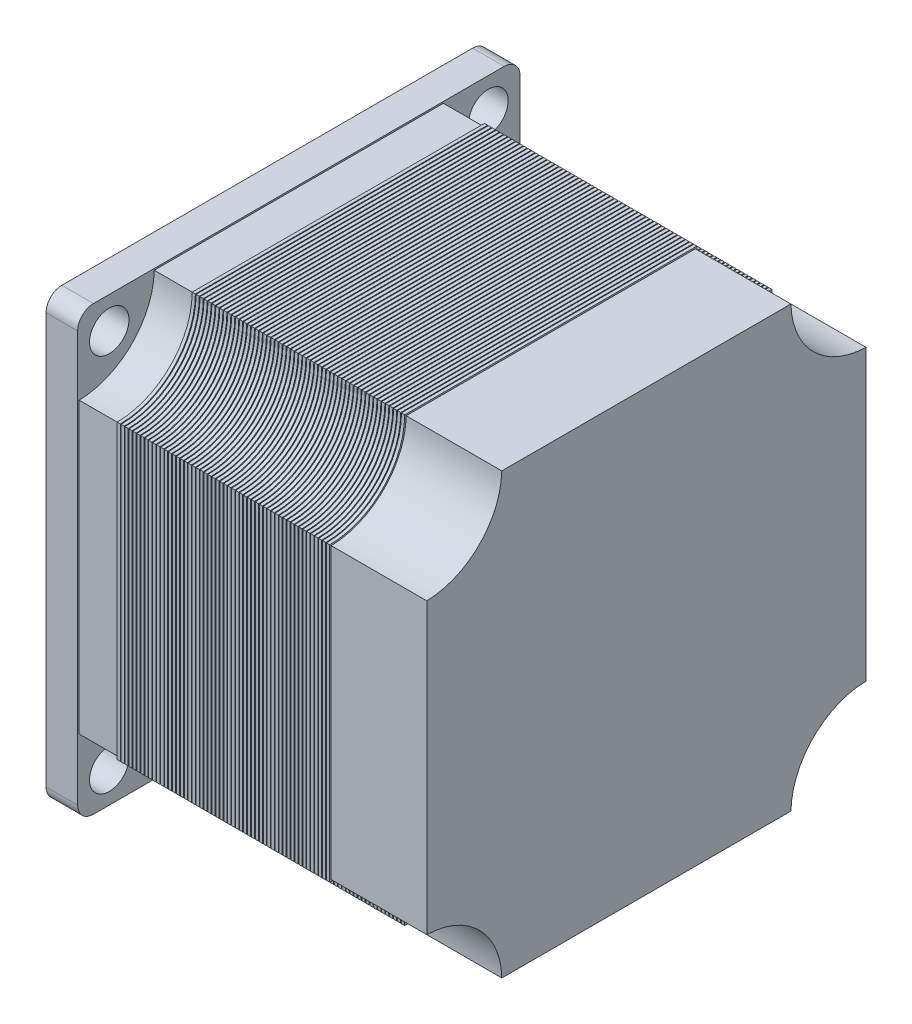
SolidWorks part; units mm, degrees
ref_plane "Front" through (0, 0, 0) normal (0, 0, 1) x (1, 0, 0)
ref_plane "Top" through (0, 0, 0) normal (0, 1, 0) x (1, 0, 0)
ref_plane "Right" through (0, 0, 0) normal (1, 0, 0) x (0, 0, -1)
sketch "Sketch1" plane through (0, 0, 0) normal (1, 0, 0) x (0, 0, -1)
  line L0 (-53.617, 0) -> (72.2837, 0) construction
  line L1 (-18.5, 28) -> (18.5, 28)
  line L2 (-28, 18.5) -> (-28, -18.5)
  line L3 (-18.5, -28) -> (18.5, -28)
  line L4 (28, 18.5) -> (28, -18.5)
  line L5 (-28, 28) -> (28, -28) construction
  line L6 (-28, -28) -> (28, 28) construction
  line L7 (0, 48.9504) -> (0, -61.2624) construction
  arc A0 (18.5, 28) -> (28, 18.5) centre (28, 28) ccw
  arc A1 (28, -18.5) -> (18.5, -28) centre (28, -28) ccw
  arc A2 (-18.5, -28) -> (-28, -18.5) centre (-28, -28) ccw
  arc A3 (-28, 18.5) -> (-18.5, 28) centre (-28, 28) ccw
  circle A4 centre (0, 0) radius 3
  point P0 (0, 0)
  point P19 (0, 0)
  dimension "D1" = 6
  dimension "D2" = 56
  dimension "D4" = 37
  dimension "D6" = 28
  dimension "D7" = 28
  dimension "D3" = 4
extrude "Boss-Extrude1" add sketch "Sketch1" along normal blind 27
sketch "Sketch6" plane through (27, 0, 0) normal (1, 0, 0) x (0, 0, -1)
  line L8 (18.3021, 27.8) -> (-18.3021, 27.8)
  line L9 (-27.8, 18.3021) -> (-27.8, -18.3021)
  line L10 (-18.3021, -27.8) -> (18.3021, -27.8)
  line L11 (27.8, -18.3021) -> (27.8, 18.3021)
  line L12 (18.3021, 27.8) -> (-18.3021, 27.8)
  line L13 (-27.8, 18.3021) -> (-27.8, -18.3021)
  line L14 (-18.3021, -27.8) -> (18.3021, -27.8)
  line L15 (27.8, -18.3021) -> (27.8, 18.3021)
  line L16 (28, -18.5) -> (28, 18.5)
  line L17 (-18.5, -28) -> (18.5, -28)
  line L18 (-28, 18.5) -> (-28, -18.5)
  line L19 (18.5, 28) -> (-18.5, 28)
  line L20 (28, -18.5) -> (28, 18.5)
  line L21 (-18.5, -28) -> (18.5, -28)
  line L22 (-28, 18.5) -> (-28, -18.5)
  line L23 (18.5, 28) -> (-18.5, 28)
  arc A8 (18.3021, 27.8) -> (27.8, 18.3021) centre (28, 28) ccw
  arc A9 (-27.8, 18.3021) -> (-18.3021, 27.8) centre (-28, 28) ccw
  arc A10 (-18.3021, -27.8) -> (-27.8, -18.3021) centre (-28, -28) ccw
  arc A11 (27.8, -18.3021) -> (18.3021, -27.8) centre (28, -28) ccw
  arc A12 (18.3021, 27.8) -> (27.8, 18.3021) centre (28, 28) ccw
  arc A13 (-27.8, 18.3021) -> (-18.3021, 27.8) centre (-28, 28) ccw
  arc A14 (-18.3021, -27.8) -> (-27.8, -18.3021) centre (-28, -28) ccw
  arc A15 (27.8, -18.3021) -> (18.3021, -27.8) centre (28, -28) ccw
  arc A16 (18.5, 28) -> (28, 18.5) centre (28, 28) ccw
  arc A17 (28, -18.5) -> (18.5, -28) centre (28, -28) ccw
  arc A18 (-18.5, -28) -> (-28, -18.5) centre (-28, -28) ccw
  arc A19 (-28, 18.5) -> (-18.5, 28) centre (-28, 28) ccw
  arc A20 (18.5, 28) -> (28, 18.5) centre (28, 28) ccw
  arc A21 (28, -18.5) -> (18.5, -28) centre (28, -28) ccw
  arc A22 (-18.5, -28) -> (-28, -18.5) centre (-28, -28) ccw
  arc A23 (-28, 18.5) -> (-18.5, 28) centre (-28, 28) ccw
  dimension "D1" = 0.2
  dimension "D2" = 0
extrude "Cut-Extrude4" cut sketch "Sketch6" against normal blind 0.1
pattern_linear "LPattern5" count 55 spacing 0.5 along (-1, 0, 0) of "Cut-Extrude4"
sketch "Sketch10" plane through (27, 0, 0) normal (1, 0, 0) x (0, 0, -1)
  line L4 (27.8, -18.3021) -> (27.8, 18.3021)
  line L5 (27.8, -18.3021) -> (27.8, 18.3021)
  line L6 (18.3021, 27.8) -> (-18.3021, 27.8)
  line L7 (18.3021, 27.8) -> (-18.3021, 27.8)
  line L12 (-27.8, 18.3021) -> (-27.8, -18.3021)
  line L13 (-27.8, 18.3021) -> (-27.8, -18.3021)
  line L14 (-18.3021, -27.8) -> (18.3021, -27.8)
  line L15 (-18.3021, -27.8) -> (18.3021, -27.8)
  arc A4 (18.3021, 27.8) -> (27.8, 18.3021) centre (28, 28) ccw
  arc A5 (18.3021, 27.8) -> (27.8, 18.3021) centre (28, 28) ccw
  arc A6 (-27.8, 18.3021) -> (-18.3021, 27.8) centre (-28, 28) ccw
  arc A7 (-27.8, 18.3021) -> (-18.3021, 27.8) centre (-28, 28) ccw
  arc A12 (-18.3021, -27.8) -> (-27.8, -18.3021) centre (-28, -28) ccw
  arc A13 (-18.3021, -27.8) -> (-27.8, -18.3021) centre (-28, -28) ccw
  arc A14 (27.8, -18.3021) -> (18.3021, -27.8) centre (28, -28) ccw
  arc A15 (27.8, -18.3021) -> (18.3021, -27.8) centre (28, -28) ccw
  dimension "D1" = 0
extrude "Boss-Extrude4" add sketch "Sketch10" along normal blind 12
sketch "Sketch12" plane through (0, 0, 0) normal (-1, 0, 0) x (0, 0, 1)
  line L4 (-27.8, 18.3021) -> (-27.8, -18.3021)
  line L5 (18.3021, 27.8) -> (-18.3021, 27.8)
  line L6 (27.8, -18.3021) -> (27.8, 18.3021)
  line L7 (-18.3021, -27.8) -> (18.3021, -27.8)
  line L8 (-27.8, 18.3021) -> (-27.8, -18.3021)
  line L9 (18.3021, 27.8) -> (-18.3021, 27.8)
  line L10 (27.8, -18.3021) -> (27.8, 18.3021)
  line L11 (-18.3021, -27.8) -> (18.3021, -27.8)
  arc A4 (-18.3021, -27.8) -> (-27.8, -18.3021) centre (-28, -28) ccw
  arc A5 (-27.8, 18.3021) -> (-18.3021, 27.8) centre (-28, 28) ccw
  arc A6 (18.3021, 27.8) -> (27.8, 18.3021) centre (28, 28) ccw
  arc A7 (27.8, -18.3021) -> (18.3021, -27.8) centre (28, -28) ccw
  arc A8 (-18.3021, -27.8) -> (-27.8, -18.3021) centre (-28, -28) ccw
  arc A9 (-27.8, 18.3021) -> (-18.3021, 27.8) centre (-28, 28) ccw
  arc A10 (18.3021, 27.8) -> (27.8, 18.3021) centre (28, 28) ccw
  arc A11 (27.8, -18.3021) -> (18.3021, -27.8) centre (28, -28) ccw
  dimension "D1" = 0
extrude "Boss-Extrude5" add sketch "Sketch12" along normal blind 5
sketch "Sketch14" plane through (-5, 0, 0) normal (-1, 0, 0) x (0, 0, 1)
  line L1 (-26, 28) -> (26, 28)
  line L2 (-28, 26) -> (-28, -26)
  line L3 (-26, -28) -> (26, -28)
  line L4 (28, 26) -> (28, -26)
  line L5 (-28, 28) -> (28, -28) construction
  line L6 (-28, -28) -> (28, 28) construction
  arc A0 (-28, -26) -> (-26, -28) centre (-26, -26) ccw
  arc A1 (26, -28) -> (28, -26) centre (26, -26) ccw
  arc A2 (28, 26) -> (26, 28) centre (26, 26) ccw
  arc A3 (-28, 26) -> (-26, 28) centre (-26, 26) cw
  circle A5 centre (-24, 24) radius 2.5
  circle A6 centre (24, 24) radius 2.5
  circle A7 centre (24, -24) radius 2.5
  circle A8 centre (-24, -24) radius 2.5
  point P0 (0, 0)
  point P30 (0, 0)
  dimension "D1" = 2
  dimension "D4" = 24
  dimension "D5" = 5
  dimension "D6" = 4
  dimension "D2" = 56
  dimension "D3" = 56
extrude "Boss-Extrude7" add sketch "Sketch14" along normal blind 4
sketch "Sketch15" plane through (-9, 0, 0) normal (-1, 0, 0) x (0, 0, 1)
  circle A0 centre (0, 0) radius 19
  dimension "D1" = 38
extrude "Boss-Extrude8" add sketch "Sketch15" along normal blind 2
sketch "Sketch16" plane through (-11, 0, 0) normal (-1, 0, 0) x (0, 0, 1)
  circle A0 centre (0, 0) radius 3
  dimension "D1" = 6
extrude "Cut-Extrude6" cut sketch "Sketch16" against normal blind 10
